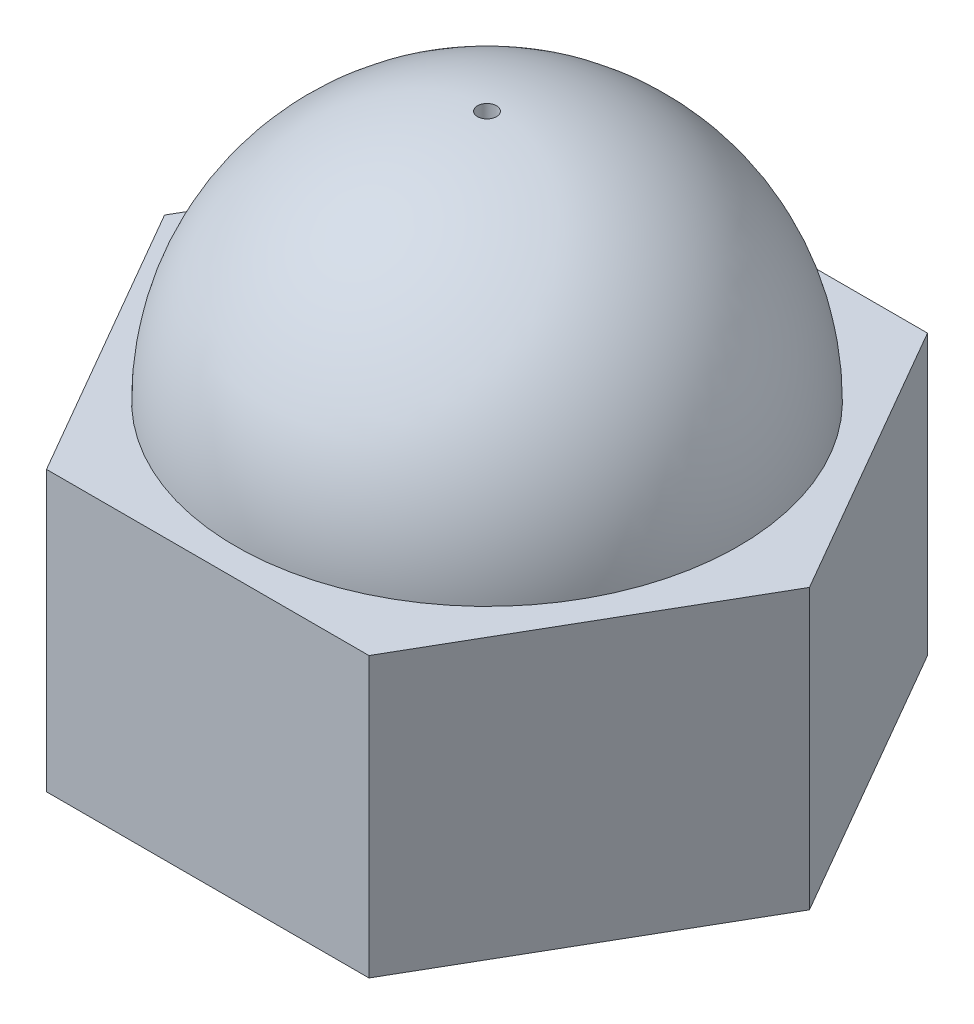
SolidWorks part; units mm, degrees
material "Brass"
ref_plane "Front Plane" through (0, 0, 0) normal (0, 0, 1) x (1, 0, 0)
ref_plane "Top Plane" through (0, 0, 0) normal (0, 1, 0) x (1, 0, 0)
ref_plane "Right Plane" through (0, 0, 0) normal (1, 0, 0) x (0, 0, -1)
ref_axis "Axis1" through (0, 0, 0) along (0, 1, 0)
sketch "Sketch1" plane through (0, 0, 0) normal (0, 1, 0) x (1, 0, 0)
  line L1 (5.7735, 0) -> (2.8868, 5)
  line L2 (2.8868, 5) -> (-2.8868, 5)
  line L3 (-2.8868, 5) -> (-5.7735, 0)
  line L4 (-5.7735, 0) -> (-2.8868, -5)
  line L5 (-2.8868, -5) -> (2.8868, -5)
  line L6 (2.8868, -5) -> (5.7735, 0)
  circle A0 centre (0, 0) radius 5 construction
  dimension "D1" = 10
extrude "Boss-Extrude1" add sketch "Sketch1" along normal blind 5
sketch "Sketch3" plane through (0, 0, 0) normal (0, 0, 1) x (1, 0, 0)
  line L0 (0, 5) -> (-4.5, 5)
  line L1 (0, 9.5) -> (0, 5)
  line L2 (0, 0) -> (0, 5.5449) construction
  arc A0 (-4.5, 5) -> (0, 9.5) centre (0, 5) cw
  dimension "D1" = 4.5
revolve "Revolve1" add sketch "Sketch3" angle 360 about axis through (0, 0, 0) along (0, 1, 0)
sketch "Sketch4" plane through (0, 0, 0) normal (0, -1, 0) x (1, 0, 0)
  circle A0 centre (0, 0) radius 3
  dimension "D1" = 6
extrude "Cut-Extrude1" cut sketch "Sketch4" against normal blind 5
sketch "Sketch6" plane through (0, 5, 0) normal (0, -1, 0) x (1, 0, 0)
  circle A0 centre (0, 0) radius 0.17
  dimension "D1" = 0.34
extrude "Cut-Extrude2" cut sketch "Sketch6" against normal through all
chamfer "Chamfer1" [suppressed] distance 1.5 distance2 2
chamfer "Chamfer2" distance 0.875 distance2 2 1 edges at (0, 5, -0.17) first distance on face at (0, 5, -0.17)
